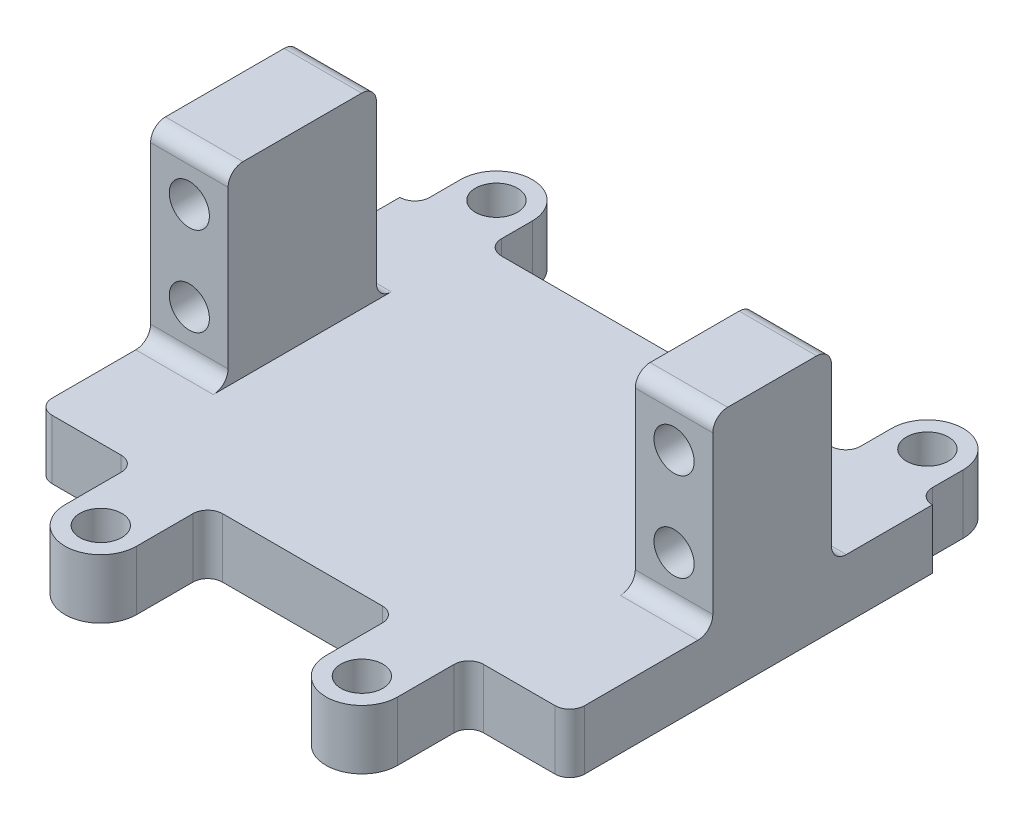
SolidWorks part; units mm, degrees
ref_plane "Front Plane" through (0, 0, 0) normal (0, 0, 1) x (1, 0, 0)
ref_plane "Top Plane" through (0, 0, 0) normal (0, 1, 0) x (1, 0, 0)
ref_plane "Right Plane" through (0, 0, 0) normal (1, 0, 0) x (0, 0, -1)
sketch "Sketch1" plane through (0, 0, 0) normal (0, 1, 0) x (1, 0, 0)
  line L1 (0, 0) -> (54.4, 0)
  line L2 (0, 0) -> (0, 38.8)
  line L3 (0, 38.8) -> (54.4, 38.8)
  line L4 (54.4, 0) -> (54.4, 38.8)
  dimension "D1" = 54.4
  dimension "D2" = 38.8
extrude "Boss-Extrude1" add sketch "Sketch1" along normal blind 3.175
sketch "Sketch2" plane through (0, 3.175, 0) normal (0, 1, 0) x (1, 0, 0)
  line L0 (0, 38.8) -> (0, 0) construction
  line L1 (0, 28) -> (7, 28)
  line L2 (0, 28) -> (0, 12.125)
  line L3 (0, 12.125) -> (7, 12.125)
  line L4 (7, 28) -> (7, 12.125)
  line L5 (54.4, 38.8) -> (0, 38.8) construction
  dimension "D1" = 15.875
  dimension "D2" = 10.8
  dimension "D3" = 7
extrude "Boss-Extrude2" add sketch "Sketch2" along normal blind 20
ref_plane "Plane1" through (27.2, 0, 0) normal (-1, 0, 0) x (0, 0, 1)
mirror "Mirror1" about plane through (27.2, 0, 0) normal (-1, 0, 0) of "Boss-Extrude2"
sketch "Sketch3" plane through (0, 3.175, 0) normal (0, 1, 0) x (1, 0, 0)
  line L0 (9.2746, -7.608) -> (9.2746, 0)
  line L1 (0, 0) -> (54.4, 0) construction
  line L2 (16.9454, -7.608) -> (16.9454, 0)
  circle A0 centre (13.11, -7.608) radius 2.2479
  circle A2 centre (13.11, -7.608) radius 3.8354
  line M12 (0, 0) -> (54.4, 0)
  dimension "D1" = 4.4958
  dimension "D4" = 1.5875
  dimension "D2" = 7.608
  dimension "D3" = 13.11
extrude "Boss-Extrude3" add sketch "Sketch3" against normal up to surface (3.175 mm away) contours A2 A0 | A2 L2 L0 M12 region at (13.11, 3.175, 2.3776) region at (13.11, 3.175, 3.8811) up to face at (27.2, 0, -19.4)
pattern_linear "LPattern1" count 2 spacing 27.94 along (1, 0, 0) of "Boss-Extrude3"
sketch "Sketch6" plane through (0, 3.175, 0) normal (0, 1, 0) x (1, 0, 0)
  line L0 (0, 38.8) -> (0, 28) construction
  line L1 (0.3048, 43.7) -> (0.3048, 38.8)
  line L2 (7.9756, 43.7) -> (7.9756, 38.8)
  line L3 (54.4, 38.8) -> (0, 38.8) construction
  circle A0 centre (4.1402, 43.7) radius 2.2479
  circle A1 centre (13.11, -7.608) radius 2.2479 construction
  circle A2 centre (4.1402, 43.7) radius 3.8354
  line M24 (54.4, 38.8) -> (0, 38.8)
  dimension "D2" = 4.4958
  dimension "D4" = 1.5875
  dimension "D1" = 51.308
  dimension "D3" = 4.1402
extrude "Boss-Extrude6" add sketch "Sketch6" against normal up to surface (3.175 mm away) contours A2 A0 | A2 L1 L2 M24 region at (4.1402, 3.175, -39.7736) region at (4.1402, 3.175, -47.4269) up to face at (27.12, 0, -3.2914)
mirror "Mirror3" about plane through (27.2, 0, 0) normal (-1, 0, 0) of "Boss-Extrude6"
sketch "Sketch7" plane through (0, 0, -28) normal (0, 0, -1) x (-1, 0, 0)
  line L0 (-7, 23.175) -> (-7, 3.175) construction
  line L1 (-7, 23.175) -> (0, 23.175) construction
  circle A0 centre (-2.8526, 17.925) radius 2.15
  circle A1 centre (-2.8526, 8.425) radius 2.15
  dimension "D1" = 4.3
  dimension "D2" = 4.1474
  dimension "D3" = 5.25
  dimension "D4" = 9.5
extrude "Cut-Extrude1" cut sketch "Sketch7" against normal up to surface (15.875 mm away) up to face at (3.5, 13.175, -12.125)
sketch "Sketch9" plane through (0, 0, 0) normal (-1, 0, 0) x (0, 0, 1)
  line L0 (-38.8, 0) -> (-38.8, 3.175) construction
  line L1 (-38.8, 0) -> (-38.8, 3.175)
  line L2 (-38.8, 3.175) -> (-28, 3.175)
  line L3 (-28, 3.175) -> (-28, 23.175)
  line L4 (-28, 23.175) -> (-12.125, 23.175)
  line L5 (-12.125, 23.175) -> (-12.125, 3.175)
  line L10 (0, 0) -> (-38.8, 0)
  line L11 (-12.125, 3.175) -> (0, 3.175)
  line L12 (0, 3.175) -> (0, 0)
extrude "Boss-Extrude7" add sketch "Sketch9" along normal blind 1.2948
mirror "Mirror4" about plane through (27.2, 0, 0) normal (-1, 0, 0) of "Boss-Extrude7"
mirror "Mirror5" about plane through (27.2, 0, 0) normal (-1, 0, 0) of "Cut-Extrude1"
sketch "Sketch11" plane through (0, 0, 0) normal (0, -1, 0) x (1, 0, 0)
  line L16 (55.6948, 0) -> (44.8854, 0)
  line L17 (-1.2948, 0) -> (-1.2948, -38.8)
  line L18 (-1.2948, -38.8) -> (0.3048, -38.8)
  line L19 (0.3048, -38.8) -> (0.3048, -43.7)
  line L20 (7.9756, -43.7) -> (7.9756, -38.8)
  line L21 (0.3048, -38.8) -> (0.3048, -43.7)
  line L22 (46.4244, -38.8) -> (46.4244, -43.7)
  line L23 (7.9756, -38.8) -> (46.4244, -38.8)
  line L24 (54.0952, -38.8) -> (55.6948, -38.8)
  line L25 (55.6948, -38.8) -> (55.6948, 0)
  line L26 (55.6948, 0) -> (44.8854, 0)
  line L27 (44.8854, 0) -> (44.8854, 7.608)
  line L28 (37.2146, 7.608) -> (37.2146, 0)
  line L29 (37.2146, 0) -> (16.9454, 0)
  line L30 (16.9454, 0) -> (16.9454, 7.608)
  line L31 (9.2746, 7.608) -> (9.2746, 0)
  line L33 (-1.2948, 0) -> (-1.2948, -38.8)
  line L34 (-1.2948, -38.8) -> (0.3048, -38.8)
  line L36 (7.9756, -43.7) -> (7.9756, -38.8)
  line L38 (46.4244, -38.8) -> (46.4244, -43.7)
  line L40 (54.0952, -38.8) -> (55.6948, -38.8)
  line L41 (55.6948, -38.8) -> (55.6948, 0)
  line L43 (44.8854, 0) -> (44.8854, 7.608)
  line L44 (37.2146, 7.608) -> (37.2146, 0)
  line L46 (16.9454, 0) -> (16.9454, 7.608)
  line L47 (9.2746, 7.608) -> (9.2746, 0)
  line L48 (37.2146, 0) -> (16.9454, 0)
  line L49 (9.2746, 0) -> (-1.2948, 0)
  line L50 (9.2746, 0) -> (-1.2948, 0)
  line L51 (7.9756, -38.8) -> (46.4244, -38.8)
  line L52 (54.0952, -43.7) -> (54.0952, -38.8)
  line L53 (54.0952, -43.7) -> (54.0952, -38.8)
  circle A0 centre (4.1402, -43.7) radius 2.2479 construction
  circle A1 centre (50.2598, -43.7) radius 2.2479 construction
  circle A2 centre (41.05, 7.608) radius 2.2479 construction
  circle A3 centre (13.11, 7.608) radius 2.2479 construction
  circle A4 centre (4.1402, -43.7) radius 2.2479
  circle A5 centre (50.2598, -43.7) radius 2.2479
  circle A6 centre (41.05, 7.608) radius 2.2479
  circle A7 centre (13.11, 7.608) radius 2.2479
  arc A16 (0.3048, -43.7) -> (7.9756, -43.7) centre (4.1402, -43.7) ccw
  arc A19 (46.4244, -43.7) -> (54.0952, -43.7) centre (50.2598, -43.7) ccw
  arc A23 (44.8854, 7.608) -> (37.2146, 7.608) centre (41.05, 7.608) ccw
  arc A26 (16.9454, 7.608) -> (9.2746, 7.608) centre (13.11, 7.608) ccw
  arc A30 (0.3048, -43.7) -> (7.9756, -43.7) centre (4.1402, -43.7) ccw
  arc A33 (46.4244, -43.7) -> (54.0952, -43.7) centre (50.2598, -43.7) ccw
  arc A37 (44.8854, 7.608) -> (37.2146, 7.608) centre (41.05, 7.608) ccw
  arc A40 (16.9454, 7.608) -> (9.2746, 7.608) centre (13.11, 7.608) ccw
  dimension "D1" = 0
extrude "Boss-Extrude8" add sketch "Sketch11" along normal blind 3.175
sketch "Sketch13" plane through (55.6948, 0, 0) normal (1, 0, 0) x (0, 0, -1)
  line L1 (12.125, 23.175) -> (15.3, 23.175)
  line L2 (12.125, 23.175) -> (12.125, 3.175)
  line L3 (12.125, 3.175) -> (15.3, 3.175)
  line L4 (15.3, 23.175) -> (15.3, 3.175)
  point P5 (0, 0)
  dimension "D1" = 3.175
extrude "Cut-Extrude2" cut sketch "Sketch13" against normal up to next
fillet "Fillet1" radius 1.5875 18 edges at (-1.2948, 0, 0) (0.3048, 0, -38.8) (7.9756, 0, -38.8) (46.4244, 0, -38.8) (54.0952, 0, -38.8) (55.6948, 0, 0) (44.8854, 0, 0) (37.2146, 0, 0) (16.9454, 0, 0) (9.2746, 0, 0) (2.8526, 23.175, -12.125) (2.8526, 3.175, -12.125) (2.8526, 3.175, -28) (2.8526, 23.175, -28) (51.5474, 23.175, -28) (51.5474, 3.175, -28) (51.5474, 23.175, -15.3) (51.5474, 3.175, -15.3)
